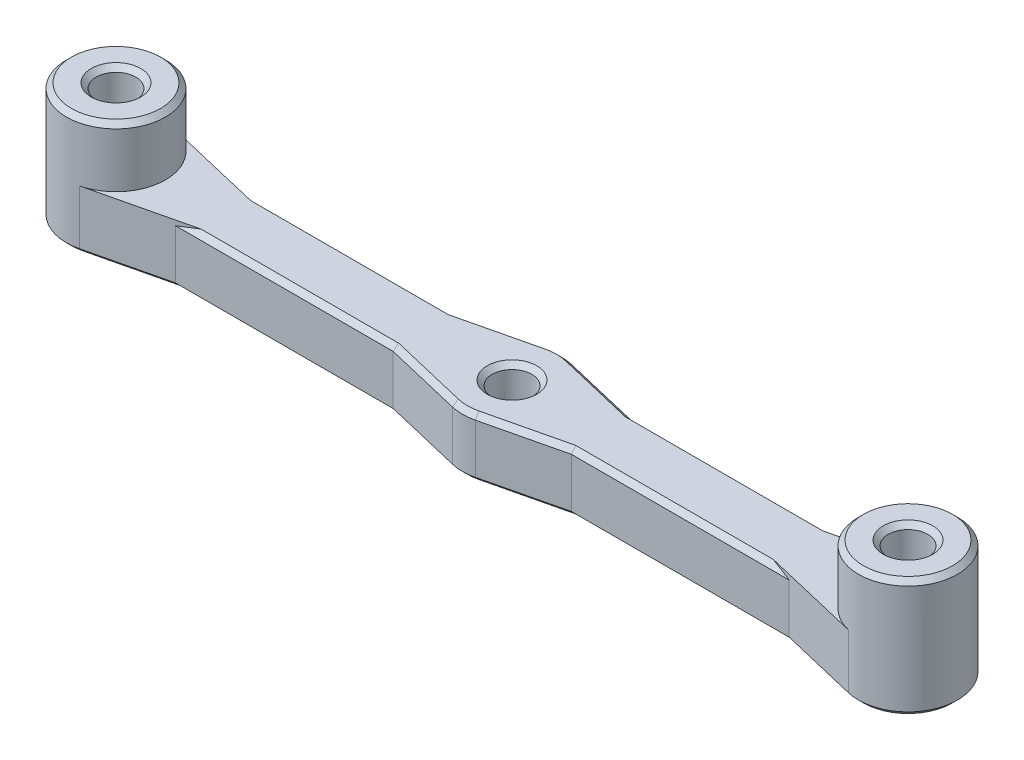
SolidWorks part; units mm, degrees
ref_plane "前视基准面" through (0, 0, 0) normal (0, 0, 1) x (1, 0, 0)
ref_plane "上视基准面" through (0, 0, 0) normal (0, 1, 0) x (1, 0, 0)
ref_plane "右视基准面" through (0, 0, 0) normal (1, 0, 0) x (0, 0, -1)
other "Configuration Table"
sketch "草图1" plane through (0, 0, 0) normal (0, 1, 0) x (1, 0, 0)
  line L0 (-20, 0) -> (20, 0) construction
  line L1 (-18, 1.5) -> (-2, 1.5)
  line L2 (2, -1.5) -> (18, -1.5)
  line L3 (2, 1.5) -> (18, 1.5)
  line L4 (-18, -1.5) -> (-2, -1.5)
  arc A0 (2, 1.5) -> (-2, 1.5) centre (0, 0) ccw
  arc A1 (18, -1.5) -> (18, 1.5) centre (20, 0) ccw
  arc A2 (-18, 1.5) -> (-18, -1.5) centre (-20, 0) ccw
  circle A3 centre (-20, 0) radius 1
  circle A4 centre (0, 0) radius 1
  circle A5 centre (20, 0) radius 1
  arc A6 (-2, -1.5) -> (2, -1.5) centre (0, 0) ccw
  point P6 (0, 0)
  dimension "D1" = 5
  dimension "D3" = 5
  dimension "D4" = 5
  dimension "D5" = 2
  dimension "D6" = 2
  dimension "D7" = 2
  dimension "D2" = 40
  dimension "D8" = 3
extrude "凸台-拉伸1" add sketch "草图1" along normal blind 3
sketch "草图2" plane through (0, 0, 0) normal (0, 1, 0) x (1, 0, 0)
  line L0 (4.5, 1.5) -> (0.5781, 2.4322)
  line L1 (4.5, -1.5) -> (0.5781, -2.4322)
  line L2 (15.5, 1.5) -> (19.4219, 2.4322)
  line L3 (15.5, -1.5) -> (19.4219, -2.4322)
  line L4 (-18, -1.5) -> (-2, -1.5)
  line L5 (2, -1.5) -> (18, -1.5)
  line L6 (18, 1.5) -> (2, 1.5)
  line L7 (-2, 1.5) -> (-18, 1.5)
  line L9 (2, -1.5) -> (4.5, -1.5)
  line L10 (18, 1.5) -> (15.5, 1.5)
  line L12 (0, -1000) -> (0, 49000) construction
  line L13 (15.5, -1.5) -> (18, -1.5)
  line L14 (4.5, 1.5) -> (2, 1.5)
  line L15 (-4.5, 1.5) -> (-2, 1.5)
  line L16 (-15.5, -1.5) -> (-18, -1.5)
  line L17 (-18, 1.5) -> (-15.5, 1.5)
  line L18 (-2, -1.5) -> (-4.5, -1.5)
  line L19 (-15.5, -1.5) -> (-19.4219, -2.4322)
  line L20 (-15.5, 1.5) -> (-19.4219, 2.4322)
  line L21 (-4.5, -1.5) -> (-0.5781, -2.4322)
  line L22 (-4.5, 1.5) -> (-0.5781, 2.4322)
  arc A0 (19.4219, 2.4322) -> (18, 1.5) centre (20, 0) ccw
  arc A1 (-2, 1.5) -> (-0.5781, 2.4322) centre (0, 0) cw
  arc A2 (-18, -1.5) -> (-19.4219, -2.4322) centre (-20, 0) cw
  arc A3 (-0.5781, -2.4322) -> (-2, -1.5) centre (0, 0) cw
  arc A4 (-18, 1.5) -> (-18, -1.5) centre (-20, 0) ccw
  arc A5 (-2, -1.5) -> (2, -1.5) centre (0, 0) ccw
  arc A6 (18, -1.5) -> (18, 1.5) centre (20, 0) ccw
  arc A7 (2, 1.5) -> (-2, 1.5) centre (0, 0) ccw
  arc A9 (0.5781, -2.4322) -> (2, -1.5) centre (0, 0) ccw
  arc A10 (18, -1.5) -> (19.4219, -2.4322) centre (20, 0) ccw
  arc A11 (2, 1.5) -> (0.5781, 2.4322) centre (0, 0) ccw
  arc A12 (-19.4219, 2.4322) -> (-18, 1.5) centre (-20, 0) cw
  dimension "D2" = 2.5
  dimension "D3" = 2.5
  dimension "D4" = 2.5
  dimension "D5" = 2.5
  dimension "D1" = 0
extrude "凸台-拉伸2" add sketch "草图2" along normal up to surface (3 mm away) up to face at (0, 3, 1)
chamfer "倒角1" distance 0.25 angle 45 19 edges at (20, 0, 1) (0, 0, 1) (-20, 0, 1) (-17.4609, 0, -1.9661) (-22.5, 0, 0) (-17.4609, 0, 1.9661) (-10, 0, 1.5) (-2.5391, 0, 1.9661) (0, 0, 2.5) (2.5391, 0, 1.9661) (10, 0, 1.5) (17.4609, 0, 1.9661) (22.5, 0, 0) (17.4609, 0, -1.9661) (10, 0, -1.5) (2.5391, 0, -1.9661) (0, 0, -2.5) (-2.5391, 0, -1.9661) (-10, 0, -1.5)
sketch "草图4" plane through (0, 0, 0) normal (0, 1, 0) x (1, 0, 0)
  circle A0 centre (-20, 0) radius 1
  circle A1 centre (-20, 0) radius 2.5
  circle A2 centre (20, 0) radius 1
  circle A3 centre (20, 0) radius 2.5
  dimension "D1" = 5
  dimension "D2" = 2
  dimension "D3" = 5
  dimension "D4" = 2
extrude "凸台-拉伸3" add sketch "草图4" along normal blind 3 from surface starting at face at (0, 3, 0)
chamfer "倒角4" distance 0.25 angle 45 4 edges at (-20, 6, 1) (-20, 6, 2.5) (20, 6, 1) (20, 6, 2.5)
chamfer "倒角5" distance 0.25 angle 45 11 edges at (0, 3, 1) (10, 3, -1.5) (2.5391, 3, -1.9661) (0, 3, -2.5) (-2.5391, 3, -1.9661) (-10, 3, -1.5) (10, 3, 1.5) (2.5391, 3, 1.9661) (0, 3, 2.5) (-2.5391, 3, 1.9661) (-10, 3, 1.5)
